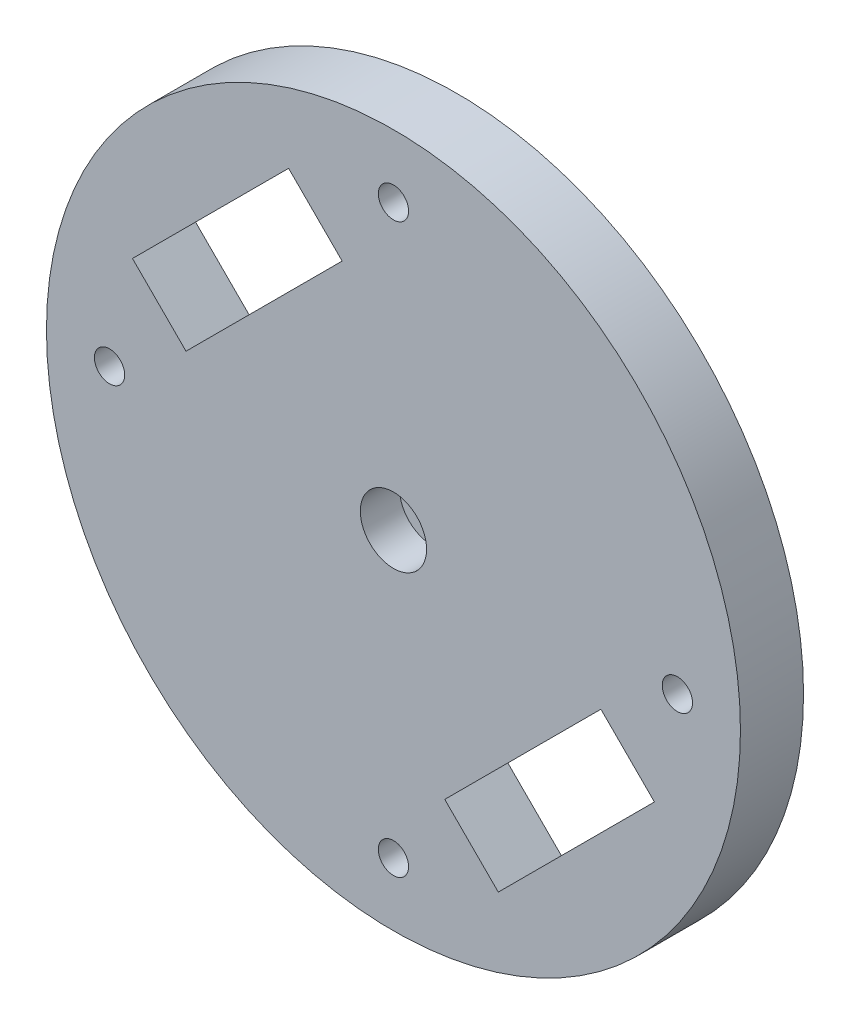
SolidWorks part; units mm, degrees
material "Plain Carbon Steel"
ref_plane "Front Plane" through (0, 0, 0) normal (0, 0, 1) x (1, 0, 0)
ref_plane "Top Plane" through (0, 0, 0) normal (0, 1, 0) x (1, 0, 0)
ref_plane "Right Plane" through (0, 0, 0) normal (1, 0, 0) x (0, 0, -1)
sketch "Sketch1" plane through (0, 0, 0) normal (0, 0, 1) x (1, 0, 0)
  circle A0 centre (0, 0) radius 7.5
  dimension "D1" = 15
extrude "Boss-Extrude1" add sketch "Sketch1" along normal blind 20.05
sketch "Sketch3" plane through (0, 0, 0) normal (0, 0, -1) x (-1, 0, 0)
  line L0 (0, 55) -> (0, -55) construction
  line L1 (-2.5, 5) -> (2.5, 5)
  line L2 (-2.5, 5) -> (-2.5, 10)
  line L3 (-2.5, 10) -> (2.5, 10)
  line L4 (2.5, 5) -> (2.5, 10)
  line L5 (-2.5, 5) -> (2.5, 10) construction
  line L6 (-2.5, 10) -> (2.5, 5) construction
  circle A0 centre (0, 0) radius 7.5 construction
  point P0 (0, 7.5)
  dimension "D1" = 2.5
  dimension "D2" = 5
extrude "Cut-Extrude1" cut sketch "Sketch3" against normal blind 21
sketch "Sketch6" plane through (0, 0, 20.05) normal (0, 0, 1) x (1, 0, 0)
  circle A0 centre (0, 0) radius 8.5
  dimension "D1" = 17
extrude "Boss-Extrude2" add sketch "Sketch6" along normal blind 24
sketch "Sketch7" plane through (0, 0, 44.05) normal (0, 0, 1) x (1, 0, 0)
  circle A0 centre (0, 0) radius 11.25
  dimension "D1" = 22.5
extrude "Boss-Extrude3" add sketch "Sketch7" along normal blind 5
sketch "Sketch8" plane through (0, 0, 49.05) normal (0, 0, 1) x (1, 0, 0)
  circle A0 centre (0, 0) radius 55
extrude "Boss-Extrude4" add sketch "Sketch8" along normal blind 10
fillet "Fillet1" radius 0.6 1 edges at (8.5, 0, 44.05)
fillet "Fillet2" radius 5 1 edges at (11.25, 0, 49.05)
hole_wizard "M4 Clearance Hole1" positions "Sketch9" profile "Sketch10" hole size "M4" standard "ANSI Metric" end condition up to next
sketch "Sketch9" plane through (0, 0, 59.05) normal (0, 0, 1) x (1, 0, 0)
  circle A0 centre (0, 0) radius 45
  point P0 (0, 45)
  point P2 (0, -45)
  point P4 (45, 0)
  point P6 (-45, 0)
  dimension "D1" = 90
sketch "Sketch10" plane through (0, 45, 59.05) normal (1, 0, 0) x (0, -1, 0)
  line L0 (0, 0) -> (0, 10)
  line L1 (0, 10) -> (2.4, 10)
  line L2 (2.4, 10) -> (2.4, 0)
  line L5 (2.4, 0) -> (0, 0)
  line L11 (0, -6.35) -> (0, 107.95) construction
  dimension "Thru Hole Dia." = 4.8
  dimension "Thru Hole Depth" = 10
hole_wizard "M6x1.0 Tapped Hole2" positions "Sketch11" profile "Sketch12" tap size "M6x1.0" standard "ANSI Metric"
sketch "Sketch11" plane through (0, 0, 0) normal (0, 0, -1) x (-1, 0, 0)
  point P0 (0, 0)
sketch "Sketch12" plane through (0, 0, 0) normal (1, 0, 0) x (0, 1, 0)
  line L0 (0, 0) -> (0, 25)
  line L1 (0, 25) -> (2.5, 23.4978)
  line L2 (2.5, 23.4978) -> (2.5, 0)
  line L5 (2.5, 0) -> (0, 0)
  line L10 (0, 25) -> (-2.5, 23.4978) construction
  line L11 (0, -6.35) -> (0, 107.95) construction
  dimension "Tap Drill Dia." = 5
  dimension "Tap Drill Depth" = 25
  dimension "Drill Angle" = 118
cosmetic thread "Hole Thread5" parameters "D1"=20, "D2"=6
sketch "Sketch13" plane through (0, 0, 0) normal (0, 0, -1) x (-1, 0, 0)
  circle A0 centre (0, 0) radius 7.5
  dimension "D1" = 15
extrude "Cut-Extrude2" cut sketch "Sketch13" against normal blind 2
sketch "Sketch14" plane through (0, 0, 59.05) normal (0, 0, 1) x (1, 0, 0)
  line L0 (0, 0) -> (0, 12.4519) construction
  line L6 (-16.617, 41.3657) -> (-41.3657, 16.617)
  line L11 (0, 0) -> (-20.5061, 20.5061) construction
  line L12 (0, 0) -> (-26.2743, 0) construction
  line L13 (-41.3657, 16.617) -> (-32.8805, 8.1317)
  line L14 (-32.8805, 8.1317) -> (-8.1317, 32.8805)
  line L15 (-16.617, 41.3657) -> (-8.1317, 32.8805)
  line L16 (0, 0) -> (19.8071, 19.8071) construction
  line L17 (41.3657, -16.617) -> (16.617, -41.3657)
  line L18 (16.617, -41.3657) -> (8.1317, -32.8805)
  line L19 (8.1317, -32.8805) -> (32.8805, -8.1317)
  line L20 (41.3657, -16.617) -> (32.8805, -8.1317)
  circle A0 centre (0, 0) radius 29 construction
  point P3 (-29, 0)
  dimension "D1" = 58
  dimension "D2" = 45
  dimension "D3" = 12
  dimension "D4" = 35
extrude "Cut-Extrude3" cut sketch "Sketch14" against normal up to next
sketch "Sketch15" plane through (0, 0, 2) normal (0, 0, -1) x (-1, 0, 0)
  circle A0 centre (0, 0) radius 36.6824
extrude "Cut-Extrude4" cut sketch "Sketch15" against normal up to surface (42.05 mm away) up to face at (9.1, 0, 44.05)
sketch "Sketch16" plane through (0, 0, 59.05) normal (0, 0, 1) x (1, 0, 0)
  point P0 (0, 0)
hole_wizard "CBORE for M6 Hex Head Bolt1" positions "Sketch17" profile "Sketch18" counterbore size "M6" standard "ANSI Metric" end condition up to next
sketch "Sketch17" plane through (0, 0, 59.05) normal (0, 0, 1) x (1, 0, 0)
  point P0 (0, 0)
sketch "Sketch18" plane through (0, 0, 59.05) normal (1, 0, 0) x (0, -1, 0)
  line L0 (0, 0) -> (0, 15)
  line L1 (0, 15) -> (3, 15)
  line L3 (3, 15) -> (3, 6.2)
  line L4 (3, 6.2) -> (5.25, 6.2)
  line L5 (5.25, 6.2) -> (5.25, 0)
  line L7 (5.25, 0) -> (0, 0)
  line L11 (0, -6.35) -> (0, 107.95) construction
  dimension "Thru Hole Dia." = 6
  dimension "Thru Hole Depth" = 15
  dimension "C'Bore Dia." = 10.5
  dimension "C'Bore Depth" = 6.2
